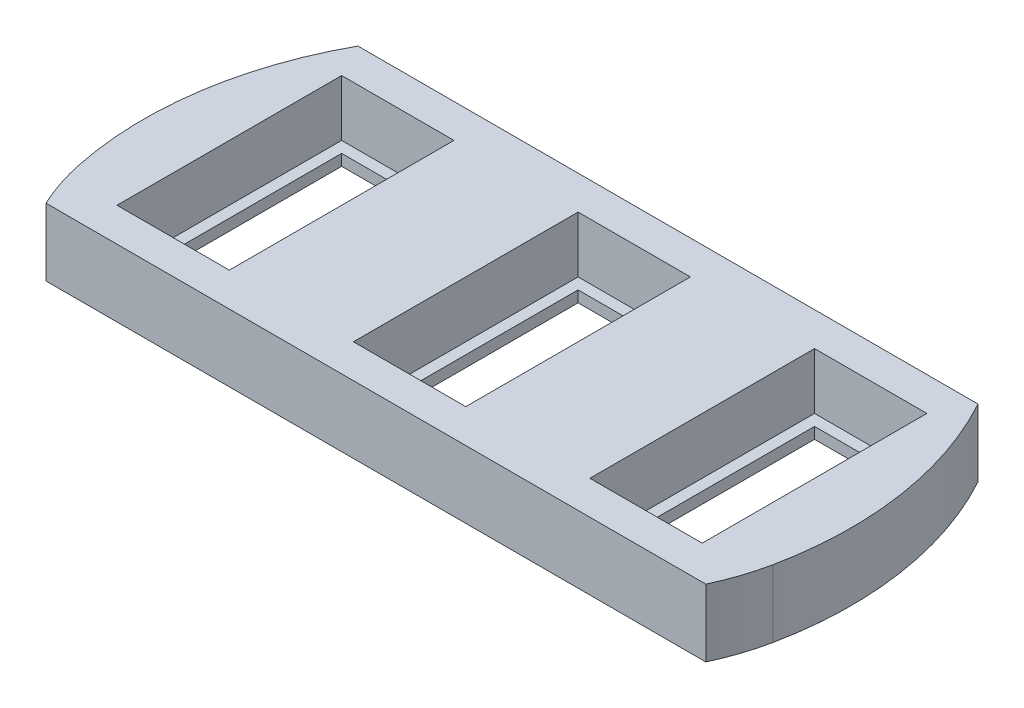
SolidWorks part; units mm, degrees
ref_plane "Plan de face" through (0, 0, 0) normal (0, 0, 1) x (1, 0, 0)
ref_plane "Plan de dessus" through (0, 0, 0) normal (0, 1, 0) x (1, 0, 0)
ref_plane "Plan de droite" through (0, 0, 0) normal (1, 0, 0) x (0, 0, -1)
sketch "Esquisse1" plane through (0, 0, 0) normal (0, 1, 0) x (1, 0, 0)
  line L0 (0, 29) -> (0, -31.5) construction
  line L1 (27.5988, 12.184) -> (-27.5988, 12.184)
  line L2 (-29.3673, -13.816) -> (29.3673, -13.816)
  line L3 (25.0482, 8.184) -> (25.0482, -9.816)
  line L4 (-26.0482, 9.184) -> (-16.0482, 9.184) construction
  line L5 (-26.0482, 9.184) -> (-26.0482, -10.816) construction
  line L6 (-26.0482, -10.816) -> (-16.0482, -10.816) construction
  line L7 (-16.0482, 9.184) -> (-16.0482, -10.816) construction
  line L8 (-26.0482, 9.184) -> (-29.0482, 9.184) construction
  line L9 (-5, 9.184) -> (5, 9.184) construction
  line L10 (-25.0482, 8.184) -> (-17.0482, 8.184)
  line L11 (-5, 9.184) -> (-5, -10.816) construction
  line L12 (-5, -10.816) -> (5, -10.816) construction
  line L13 (5, 9.184) -> (5, -10.816) construction
  line L14 (-25.0482, 8.184) -> (-25.0482, -9.816)
  line L15 (-25.0482, -9.816) -> (-17.0482, -9.816)
  line L16 (-17.0482, 8.184) -> (-17.0482, -9.816)
  line L17 (4, 8.184) -> (-4, 8.184)
  line L18 (25.0482, 8.184) -> (17.0482, 8.184)
  line L19 (4, -9.816) -> (-4, -9.816)
  line L20 (-4, 8.184) -> (-4, -9.816)
  line L21 (17.0482, 8.184) -> (17.0482, -9.816)
  line L22 (25.0482, -9.816) -> (17.0482, -9.816)
  line L23 (4, 8.184) -> (4, -9.816)
  arc A0 (31.286, -9.7222) -> (-31.286, -9.7222) centre (0, -3) ccw construction
  arc A1 (-27.9146, -17.2737) -> (27.9146, -17.2737) centre (0, 3) ccw construction
  arc A2 (-27.9146, -17.2737) -> (-31.286, -9.7222) centre (-11.7322, -5.5208) cw construction
  arc A3 (27.9146, -17.2737) -> (31.286, -9.7222) centre (11.7322, -5.5208) ccw construction
  arc A5 (30.8566, -9.3342) -> (27.5988, 12.184) centre (0, -3) ccw
  arc A6 (29.3673, -13.816) -> (30.8566, -9.3342) centre (11.2651, -5.3125) ccw
  arc A7 (-29.3673, -13.816) -> (-30.8566, -9.3342) centre (-11.2651, -5.3125) cw
  arc A8 (-27.5988, 12.184) -> (-30.8566, -9.3342) centre (0, -3) ccw
  point P10 (0, -31.5)
  point P11 (0, 29)
  point P13 (0, 0)
  point P25 (-21.0482, -9.816)
  point P26 (0, 0)
  point P30 (0, 0)
  point P37 (0, 0)
  point P39 (-29.3673, -13.816)
  point P40 (0, 0)
  point P46 (0, 0)
  point P47 (0, 0)
  point P49 (0, 0)
  dimension "D1" = 69
  dimension "D2" = 64
  dimension "D3" = 20
  dimension "D6" = 10
  dimension "D8" = 5
  dimension "D9" = 1
  dimension "D10" = 1
  dimension "D11" = 1
  dimension "D12" = 63
  dimension "D13" = 20
  dimension "D4" = 3
  dimension "D5" = 3
  dimension "D14" = 10
  dimension "D15" = 20
  dimension "D16" = 1
  dimension "D17" = 3
  dimension "D18" = 1
  dimension "D20" = 3
  dimension "D21" = 3
extrude "Boss.-Extru.1" add sketch "Esquisse1" along normal blind 1
sketch "Esquisse2" plane through (0, 1, 0) normal (0, 1, 0) x (1, 0, 0)
  line L0 (-27.5988, 12.184) -> (27.5988, 12.184)
  line L1 (29.3673, -13.816) -> (0, -13.816)
  line L2 (-21.0482, 8.184) -> (-21.0482, -9.816) construction
  line L3 (-26.0482, 9.184) -> (-16.0482, 9.184)
  line L4 (-26.0482, 9.184) -> (-26.0482, -10.816)
  line L5 (-26.0482, -10.816) -> (-16.0482, -10.816)
  line L6 (-16.0482, 9.184) -> (-16.0482, -10.816)
  line L7 (-26.0482, 9.184) -> (-16.0482, -10.816) construction
  line L8 (-26.0482, -10.816) -> (-16.0482, 9.184) construction
  line L9 (0, -13.816) -> (-29.3673, -13.816)
  line L11 (-25.0482, -0.816) -> (-17.0482, -0.816) construction
  line L14 (0, 26.0513) -> (0, -22.8455) construction
  line L15 (26.0482, 9.184) -> (26.0482, -10.816)
  line L16 (-5, 9.184) -> (5, 9.184)
  line L17 (-5, 9.184) -> (-5, -10.816)
  line L18 (-5, -10.816) -> (5, -10.816)
  line L19 (26.0482, 9.184) -> (16.0482, 9.184)
  line L20 (-5, 9.184) -> (5, -10.816) construction
  line L21 (-5, -10.816) -> (5, 9.184) construction
  line L22 (16.0482, 9.184) -> (16.0482, -10.816)
  line L23 (26.0482, -10.816) -> (16.0482, -10.816)
  line L24 (5, 9.184) -> (5, -10.816)
  line L25 (-25.0482, -9.816) -> (-17.0482, -9.816) construction
  line L26 (-17.0482, 8.184) -> (-25.0482, 8.184) construction
  line L27 (-17.0482, -9.816) -> (-17.0482, 8.184) construction
  line L28 (-25.0482, 8.184) -> (-25.0482, -9.816) construction
  arc A0 (-29.3673, -13.816) -> (-29.8056, -12.8125) centre (-11.2651, -5.3125) cw
  arc A1 (30.8566, -9.3342) -> (27.5988, 12.184) centre (0, -3) ccw
  arc A2 (30.8566, -9.3342) -> (27.5988, 12.184) centre (0, -3) ccw construction
  arc A3 (29.3673, -13.816) -> (30.8566, -9.3342) centre (11.2651, -5.3125) ccw construction
  arc A4 (-29.8056, -12.8125) -> (-30.8566, -9.3342) centre (-11.2651, -5.3125) cw
  arc A7 (29.8056, -12.8125) -> (30.8566, -9.3342) centre (11.2651, -5.3125) ccw
  arc A8 (-30.8566, -9.3342) -> (-27.5988, 12.184) centre (0, -3) cw
  arc A12 (29.3673, -13.816) -> (29.8056, -12.8125) centre (11.2651, -5.3125) ccw
  point P9 (-21.0482, -0.816)
  point P13 (0, -0.816)
  point P22 (0, 0)
  point P24 (0, 0)
  point P33 (0, 0)
  point P39 (0, -10.816)
  point P40 (0, 9.184)
  point P41 (0, -13.2612)
  point P44 (0, 12.184)
  dimension "D1" = 10
  dimension "D2" = 20
  dimension "D3" = 10
extrude "Boss.-Extru.2" add sketch "Esquisse2" along normal blind 5
